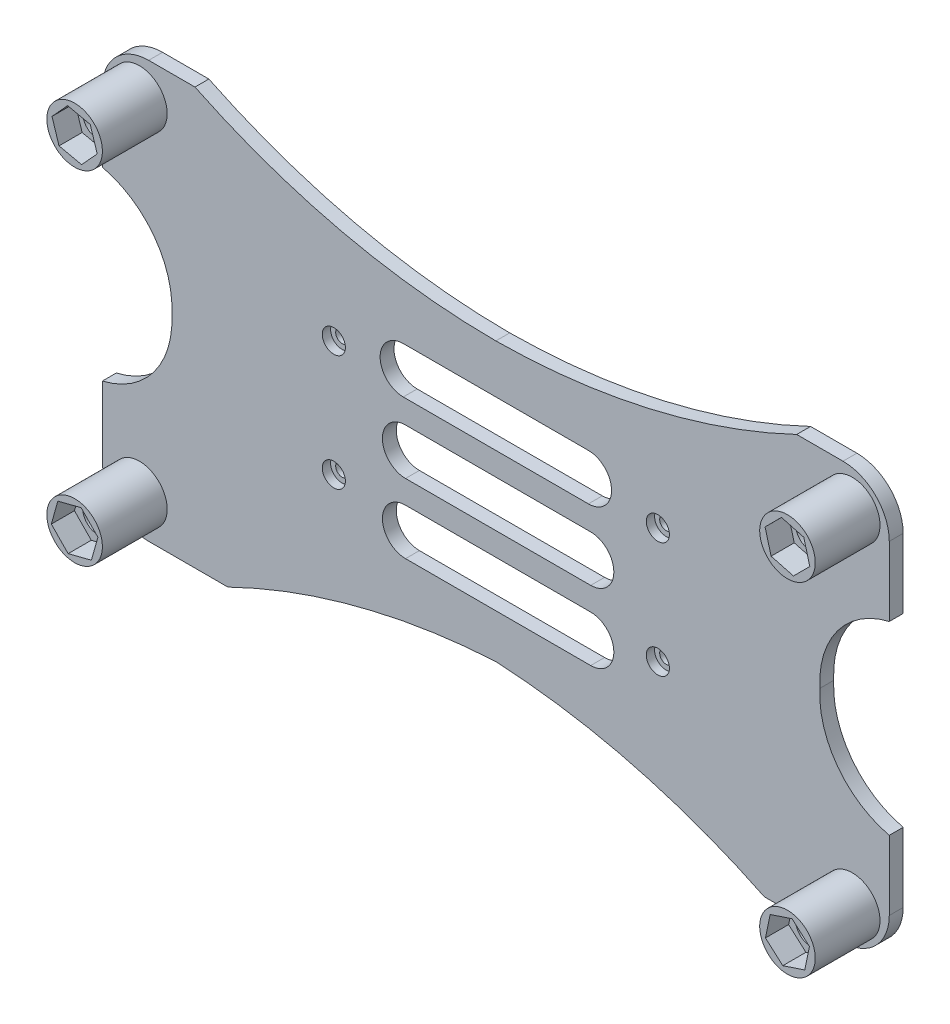
SolidWorks part; units mm, degrees
ref_plane "前视基准面" through (0, 0, 0) normal (0, 0, 1) x (1, 0, 0)
ref_plane "上视基准面" through (0, 0, 0) normal (0, 1, 0) x (1, 0, 0)
ref_plane "右视基准面" through (0, 0, 0) normal (1, 0, 0) x (0, 0, -1)
sketch "草图1" plane through (0, 0, 0) normal (0, 0, 1) x (1, 0, 0)
  line L1 (-72.5741, 45.4874) -> (77.4259, 45.4874)
  line L2 (-82.5741, 35.4874) -> (-82.5741, -34.5126)
  line L3 (-72.5741, -44.5126) -> (77.4259, -44.5126)
  line L4 (87.4259, 35.4874) -> (87.4259, -34.5126)
  arc A0 (-72.5741, 45.4874) -> (-82.5741, 35.4874) centre (-72.5741, 35.4874) ccw
  arc A1 (-72.5741, -44.5126) -> (-82.5741, -34.5126) centre (-72.5741, -34.5126) cw
  arc A2 (87.4259, 35.4874) -> (77.4259, 45.4874) centre (77.4259, 35.4874) ccw
  arc A3 (87.4259, -34.5126) -> (77.4259, -44.5126) centre (77.4259, -34.5126) cw
  dimension "D1" = 10
  dimension "D2" = 10
  dimension "D3" = 10
  dimension "D4" = 10
  dimension "D5" = 90
  dimension "D6" = 170
extrude "凸台-拉伸1" add sketch "草图1" along normal blind 3
ref_plane "for screw hole" through (0, 0, 3) normal (0, 0, 1) x (1, 0, 0)
sketch "草图2" plane through (0, 0, 3) normal (0, 0, 1) x (1, 0, 0)
  line L0 (77.4259, 45.4874) -> (-72.5741, 45.4874) construction
  line L1 (-82.5741, 35.4874) -> (-82.5741, -34.5126) construction
  line L2 (-72.5741, -44.5126) -> (77.4259, -44.5126) construction
  line L3 (87.4259, -34.5126) -> (87.4259, 35.4874) construction
  line L4 (-55.4572, -44.5126) -> (60.4378, -44.5126)
  line L5 (-62.5741, 45.4874) -> (67.4259, 45.4874)
  line L6 (87.4259, 20.4874) -> (87.4259, -19.5126)
  line L7 (-82.5741, 20.4874) -> (-82.5741, -19.5126)
  line L8 (-17.5741, 15) -> (22.4259, 15) construction
  line L9 (-17.5741, 20) -> (22.4259, 20)
  line L10 (-17.5741, 10) -> (22.4259, 10)
  line L11 (-17.0794, 0) -> (22.9206, 0) construction
  line L12 (-17.0794, 5) -> (22.9206, 5)
  line L13 (-17.0794, -5) -> (22.9206, -5)
  line L14 (-17.0794, -15) -> (22.9206, -15) construction
  line L15 (-17.0794, -10) -> (22.9206, -10)
  line L16 (-17.0794, -20) -> (22.9206, -20)
  circle A0 centre (-32.5741, 12.9874) radius 1.4
  circle A1 centre (-32.5741, -12.0126) radius 1.4
  circle A2 centre (37.4259, 12.9874) radius 1.4
  circle A3 centre (37.4259, -12.0126) radius 1.4
  arc A4 (67.4259, 45.4874) -> (2.4259, 30.4874) centre (1.0956, 184.5854) cw
  arc A5 (-62.5741, 45.4874) -> (2.4259, 30.4874) centre (2.8104, 180.4869) ccw
  arc A6 (-55.4572, -44.5126) -> (2.4259, -29.5126) centre (10.3578, -179.3027) cw
  arc A7 (60.4378, -44.5126) -> (2.4259, -29.5126) centre (-5.3618, -179.3103) ccw
  arc A8 (87.4259, 20.4874) -> (72.4259, 0.4874) centre (91.8434, 1.5492) ccw
  arc A9 (87.4259, -19.5126) -> (72.4259, 0.4874) centre (91.8434, -0.5745) cw
  arc A10 (-82.5741, 20.4874) -> (-67.5741, 0.4874) centre (-86.9917, 1.5492) cw
  arc A11 (-82.5741, -19.5126) -> (-67.5741, 0.4874) centre (-86.9917, -0.5745) ccw
  arc A12 (-17.5741, 20) -> (-17.5741, 10) centre (-17.5741, 15) ccw
  arc A13 (22.4259, 10) -> (22.4259, 20) centre (22.4259, 15) ccw
  arc A14 (-17.0794, 5) -> (-17.0794, -5) centre (-17.0794, 0) ccw
  arc A15 (22.9206, -5) -> (22.9206, 5) centre (22.9206, 0) ccw
  arc A16 (-17.0794, -10) -> (-17.0794, -20) centre (-17.0794, -15) ccw
  arc A17 (22.9206, -20) -> (22.9206, -10) centre (22.9206, -15) ccw
  point P12 (2.4259, 30.4874)
  point P13 (2.4259, -29.5126)
  point P16 (-62.5741, 45.4874)
  point P17 (67.4259, 45.4874)
  point P18 (-55.4572, -44.5126)
  point P19 (60.4378, -44.5126)
  point P29 (-67.5741, 0.4874)
  point P33 (72.4259, 0.4874)
  point P34 (-82.5741, 20.4874)
  point P35 (-82.5741, -19.5126)
  point P36 (87.4259, -19.5126)
  point P37 (87.4259, 20.4874)
  point P54 (2.4259, 15)
  point P61 (2.9206, 0)
  point P68 (2.9206, -15)
  dimension "D2" = 2.8
  dimension "D3" = 2.8
  dimension "D4" = 2.8
  dimension "D8" = 32.5
  dimension "D9" = 50
  dimension "D10" = 50
  dimension "D11" = 2.8
  dimension "D21" = 45
  dimension "D29" = 15
  dimension "D5" = 70
  dimension "D6" = 70
  dimension "D7" = 25
  dimension "D12" = 25
  dimension "D13" = 32.5
  dimension "D14" = 85
  dimension "D15" = 15
  dimension "D16" = 85
  dimension "D17" = 15
  dimension "D18" = 20
  dimension "D19" = 20
  dimension "D20" = 26.9881
  dimension "D22" = 15
  dimension "D23" = 15
  dimension "D24" = 45
  dimension "D25" = 25
  dimension "D26" = 25
  dimension "D27" = 25
  dimension "D28" = 25
  dimension "D30" = 15
  dimension "D31" = 15
extrude "切除-拉伸1" cut sketch "草图2" against normal blind 10 and the other way blind 42
ref_plane "for outer screw hole" through (0, 0, 3) normal (0, 0, 1) x (1, 0, 0)
sketch "草图3" plane through (0, 0, 3) normal (0, 0, 1) x (1, 0, 0)
  circle A0 centre (-32.5741, 12.9874) radius 2.5
  circle A1 centre (37.4259, 12.9874) radius 2.5
  circle A2 centre (37.4259, -12.0126) radius 2.5
  circle A3 centre (-32.5741, -12.0126) radius 2.5
  dimension "D1" = 5
  dimension "D2" = 5
  dimension "D3" = 5
  dimension "D4" = 5
extrude "切除-拉伸2" cut sketch "草图3" against normal blind 1.8
ref_plane "for stands" through (0, 0, 3) normal (0, 0, 1) x (1, 0, 0)
sketch "草图7" plane through (0, 0, 3) normal (0, 0, 1) x (1, 0, 0)
  line L0 (77.4259, 45.4874) -> (67.4259, 45.4874) construction
  line L1 (-82.5741, 35.4874) -> (-82.5741, 20.4874) construction
  line L2 (-72.5741, -44.5126) -> (-55.4572, -44.5126) construction
  line L3 (87.4259, -34.5126) -> (87.4259, -19.5126) construction
  circle A0 centre (-74.5741, 37.4874) radius 6
  circle A1 centre (-74.5741, -36.5126) radius 6
  circle A2 centre (79.4259, 37.4874) radius 6
  circle A3 centre (79.4259, -36.5126) radius 6
  point P12 (79.4259, -30.5126)
  point P14 (79.4259, 31.4874)
  dimension "D1" = 12
  dimension "D2" = 12
  dimension "D3" = 12
  dimension "D4" = 12
  dimension "D7" = 8
  dimension "D5" = 8
  dimension "D6" = 8
  dimension "D8" = 8
  dimension "D9" = 8
  dimension "D10" = 8
  dimension "D11" = 8
  dimension "D12" = 8
extrude "凸台-拉伸4" add sketch "草图7" along normal blind 14
ref_plane "button left hole" through (0, 0, 17) normal (0, 0, 1) x (1, 0, 0)
ref_plane "up left hole" through (0, 0, 17) normal (0, 0, 1) x (1, 0, 0)
ref_plane "up right hole" through (0, 0, 17) normal (0, 0, 1) x (1, 0, 0)
ref_plane "button right hole" through (0, 0, 17) normal (0, 0, 1) x (1, 0, 0)
sketch "草图9" plane through (0, 0, 17) normal (0, 0, 1) x (1, 0, 0)
  line L1 (-70.9446, -40.2262) -> (-69.5433, -35.2262)
  line L2 (-69.5433, -35.2262) -> (-73.1728, -31.5126)
  line L3 (-73.1728, -31.5126) -> (-78.2036, -32.7991)
  line L4 (-78.2036, -32.7991) -> (-79.6049, -37.7991)
  line L5 (-79.6049, -37.7991) -> (-75.9754, -41.5126)
  line L6 (-75.9754, -41.5126) -> (-70.9446, -40.2262)
  circle A0 centre (-74.5741, -36.5126) radius 4.497 construction
  circle A1 centre (-74.5741, -36.5126) radius 6 construction
  dimension "D1" = 5
  dimension "D2" = 0
extrude "button left nut " cut sketch "草图9" against normal blind 5
sketch "草图10" plane through (0, 0, 17) normal (0, 0, 1) x (1, 0, 0)
  line L1 (-73.0607, 32.7219) -> (-69.6904, 36.4153)
  line L2 (-69.6904, 36.4153) -> (-71.2038, 41.1808)
  line L3 (-71.2038, 41.1808) -> (-76.0876, 42.2528)
  line L4 (-76.0876, 42.2528) -> (-79.4578, 38.5594)
  line L5 (-79.4578, 38.5594) -> (-77.9444, 33.794)
  line L6 (-77.9444, 33.794) -> (-73.0607, 32.7219)
  circle A0 centre (-74.5741, 37.4874) radius 4.3301 construction
  circle A1 centre (-74.5741, 37.4874) radius 6 construction
  dimension "D1" = 5
  dimension "D2" = 0
extrude "up left nut" cut sketch "草图10" against normal blind 5
sketch "草图11" plane through (0, 0, 17) normal (0, 0, 1) x (1, 0, 0)
  line L1 (80.729, 32.6602) -> (84.2579, 36.2023)
  line L2 (84.2579, 36.2023) -> (82.9548, 41.0295)
  line L3 (82.9548, 41.0295) -> (78.1228, 42.3146)
  line L4 (78.1228, 42.3146) -> (74.5938, 38.7724)
  line L5 (74.5938, 38.7724) -> (75.897, 33.9452)
  line L6 (75.897, 33.9452) -> (80.729, 32.6602)
  circle A0 centre (79.4259, 37.4874) radius 4.3301 construction
  circle A2 centre (79.4259, 37.4874) radius 6 construction
  dimension "D2" = 0
  dimension "D1" = 5
extrude "up right nut" cut sketch "草图11" against normal blind 5
sketch "草图12" plane through (0, 0, 17) normal (0, 0, 1) x (1, 0, 0)
  line L1 (83.1629, -39.8344) -> (84.1712, -34.9371)
  line L2 (84.1712, -34.9371) -> (80.4341, -31.6153)
  line L3 (80.4341, -31.6153) -> (75.6888, -33.1908)
  line L4 (75.6888, -33.1908) -> (74.6806, -38.0881)
  line L5 (74.6806, -38.0881) -> (78.4176, -41.4099)
  line L6 (78.4176, -41.4099) -> (83.1629, -39.8344)
  circle A0 centre (79.4259, -36.5126) radius 4.3301 construction
  circle A1 centre (79.4259, -36.5126) radius 6 construction
  dimension "D2" = 0
  dimension "D1" = 5
extrude "button right nut" cut sketch "草图12" against normal blind 5
ref_plane "基准面13" through (0, 0, 17) normal (0, 0, 1) x (1, 0, 0)
ref_plane "基准面14" through (0, 0, 17) normal (0, 0, 1) x (1, 0, 0)
ref_plane "基准面15" through (0, 0, 17) normal (0, 0, 1) x (1, 0, 0)
ref_plane "基准面16" through (0, 0, 17) normal (0, 0, 1) x (1, 0, 0)
sketch "草图13" plane through (0, 0, 17) normal (0, 0, 1) x (1, 0, 0)
  circle A0 centre (-74.5741, -36.5126) radius 3.25
  dimension "D1" = 6.5
extrude "切除-拉伸7" cut sketch "草图13" against normal blind 13
sketch "草图15" plane through (0, 0, 17) normal (0, 0, 1) x (1, 0, 0)
  circle A0 centre (-74.5741, 37.4874) radius 3.25
  circle A1 centre (-74.5741, 37.4874) radius 6 construction
  dimension "D1" = 6.5
  dimension "D2" = 0
extrude "切除-拉伸8" cut sketch "草图15" against normal blind 13
sketch "草图16" plane through (0, 0, 17) normal (0, 0, 1) x (1, 0, 0)
  circle A0 centre (79.4259, 37.4874) radius 3.25
  dimension "D1" = 6.5
extrude "切除-拉伸9" cut sketch "草图16" against normal blind 13
sketch "草图17" plane through (0, 0, 17) normal (0, 0, 1) x (1, 0, 0)
  circle A0 centre (79.4259, -36.5126) radius 3.25
  circle A1 centre (79.4259, -36.5126) radius 6 construction
  point P4 (79.4259, -36.2982)
  point P5 (79.4259, -36.2982)
  point P6 (79.4259, -36.2982)
  point P7 (79.4259, -36.2982)
  dimension "D1" = 6.5
  dimension "D2" = 0
extrude "切除-拉伸10" cut sketch "草图17" against normal blind 13
